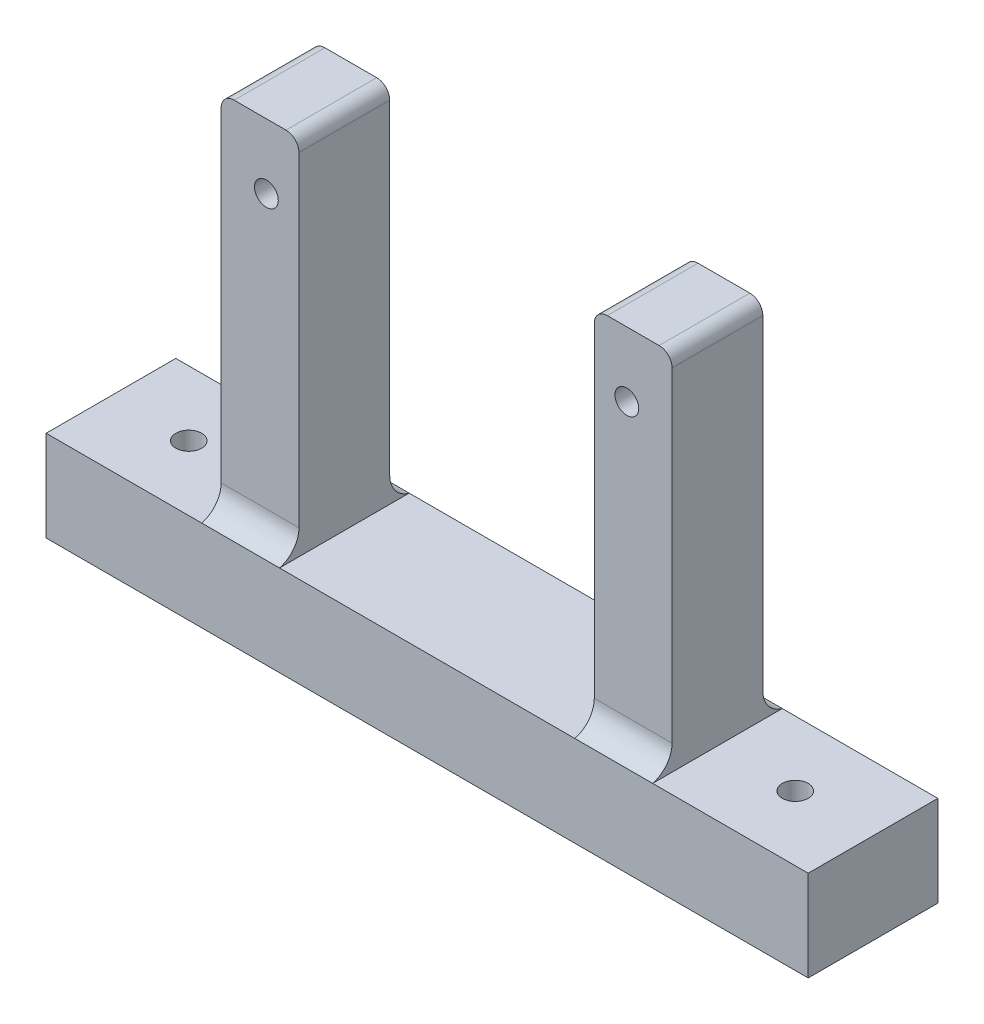
SolidWorks part; units mm, degrees
ref_plane "Front Plane" through (0, 0, 0) normal (0, 0, 1) x (1, 0, 0)
ref_plane "Top Plane" through (0, 0, 0) normal (0, 1, 0) x (1, 0, 0)
ref_plane "Right Plane" through (0, 0, 0) normal (1, 0, 0) x (0, 0, -1)
sketch "Sketch1" plane through (0, 0, 0) normal (0, 1, 0) x (1, 0, 0)
  line L1 (-29.39, -5) -> (29.39, -5)
  line L2 (-29.39, -5) -> (-29.39, 5)
  line L3 (-29.39, 5) -> (29.39, 5)
  line L4 (29.39, -5) -> (29.39, 5)
  line L5 (-29.39, -5) -> (29.39, 5) construction
  line L6 (-29.39, 5) -> (29.39, -5) construction
  point P0 (0, 0)
  dimension "D1" = 10
  dimension "D2" = 58.78
extrude "Base" add sketch "Sketch1" along normal blind 7
sketch "Sketch4" plane through (0, 0, 0) normal (0, 0, 1) x (1, 0, 0)
  line L0 (-29.39, 0) -> (29.39, 0) construction
  line L1 (-11.39, 0) -> (-17.39, 0)
  line L2 (-11.39, 0) -> (-11.39, 35)
  line L3 (-11.39, 35) -> (-17.39, 35)
  line L4 (-17.39, 0) -> (-17.39, 35)
  line L6 (11.39, 0) -> (17.39, 0)
  line L7 (11.39, 0) -> (11.39, 35)
  line L8 (11.39, 35) -> (17.39, 35)
  line L9 (17.39, 0) -> (17.39, 35)
  circle A0 centre (-13.9, 30) radius 0.915
  circle A1 centre (13.9, 30) radius 0.915
  point P15 (14.39, 35)
  dimension "D5" = 1.83
  dimension "D6" = 1.83
  dimension "D1" = 22.78
  dimension "D2" = 11.39
  dimension "D3" = 6
  dimension "D4" = 6
  dimension "D7" = 27.8
  dimension "D8" = 13.9
  dimension "D9" = 30
  dimension "D10" = 35
  dimension "D11" = 35
extrude "Flange" add sketch "Sketch4" along normal mid plane 7
sketch "Hole" plane through (0, 7, 0) normal (0, 1, 0) x (1, 0, 0)
  line L2 (-17.39, 3.5) -> (-17.39, -3.5) construction
  line L3 (17.39, -3.5) -> (17.39, 3.5) construction
  circle A0 centre (-23.39, 0) radius 1
  circle A1 centre (23.39, 0) radius 1
  dimension "D1" = 2
  dimension "D2" = 2
  dimension "D3" = 6
  dimension "D4" = 6
extrude "Bottom Hole" cut sketch "Hole" against normal up to vertex (7 mm away) up to point (0, 0, 0)
fillet "Bottom Fillet" radius 2 4 edges at (-14.39, 7, -3.5) (14.39, 7, -3.5) (14.39, 7, 3.5) (-14.39, 7, 3.5)
fillet "Top Fillet" radius 1 4 edges at (11.39, 35, 0) (17.39, 35, 0) (-11.39, 35, 0) (-17.39, 35, 0)
